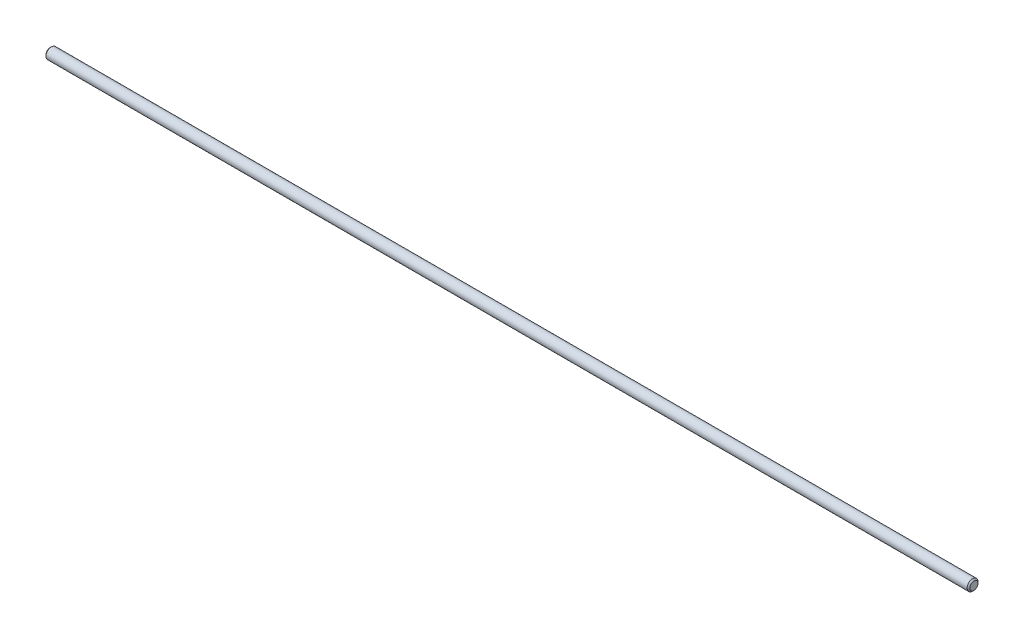
SolidWorks part; units mm, degrees
ref_plane "Front Plane" through (0, 0, 0) normal (0, 0, 1) x (1, 0, 0)
ref_plane "Top Plane" through (0, 0, 0) normal (0, 1, 0) x (1, 0, 0)
ref_plane "Right Plane" through (0, 0, 0) normal (1, 0, 0) x (0, 0, -1)
sketch "Sketch1" plane through (0, 0, 0) normal (0, 0, 1) x (1, 0, 0)
  line L0 (-85, 0) -> (85, 0) construction
  line L1 (85, 1) -> (85, -1) construction
  line L2 (-85, 1) -> (-85, -1) construction
  point P6 (83.6, -1)
  dimension "D1" = 1.4
  dimension "Thread Diameter" = 2
  dimension "Length" = 170
sketch "Sketch2" plane through (0, 0, 0) normal (1, 0, 0) x (0, 0, -1)
  circle A0 centre (0, 0) radius 1
extrude "Boss-Extrude1" add sketch "Sketch2" against normal up to vertex (85 mm away) and the other way up to vertex (85 mm away) up to point (-85, 0, 0) other way up to point (85, 0, 0)
sketch "Sketch3" plane through (85, 0, 0) normal (1, 0, 0) x (0, 0, -1)
  circle A1 centre (0, 0) radius 1
  circle A2 centre (0, 0) radius 1
  dimension "D1" = 0
curve "Helix/Spiral1" pitch 0.4 height 101 turns 252.5
sketch "Sketch4" plane through (0, 0, 0) normal (0, 0, 1) x (1, 0, 0)
  line L1 (84.9714, 1.0495) -> (85.3714, 1.0495) construction
  line L2 (84.9714, 1.0495) -> (85.1714, 0.7031) construction
  line L3 (85.1714, 0.7031) -> (85.3714, 1.0495) construction
  line L4 (85.1714, 1.0495) -> (85.1714, 1) construction
  line L5 (85.1714, 0.7031) -> (85.1714, 0.7526) construction
  line L6 (85.1429, 0.7526) -> (85.2, 0.7526) construction
  line L7 (85, 1) -> (85.3429, 1) construction
  line L8 (85, 1) -> (85.1429, 0.7526)
  line L9 (85.1429, 0.7526) -> (85.2, 0.7526)
  line L10 (85.2, 0.7526) -> (85.3429, 1)
  line L11 (85.3429, 1) -> (85, 1)
  dimension "Pitch" = 0.4
  dimension "D2" = 0.0571
sketch "Sketch5" plane through (85, 0, 0) normal (1, 0, 0) x (0, 0, -1)
  circle A0 centre (0, 0) radius 0.7526
extrude "Cut-Extrude1" cut sketch "Sketch5" against normal through all draft 45 flip side to cut
mirror "Mirror1" about plane through (0, 0, 0) normal (1, 0, 0) of "Cut-Extrude1"
equation "\"D2@Sketch4\" = \"Pitch@Sketch4\"/7"
